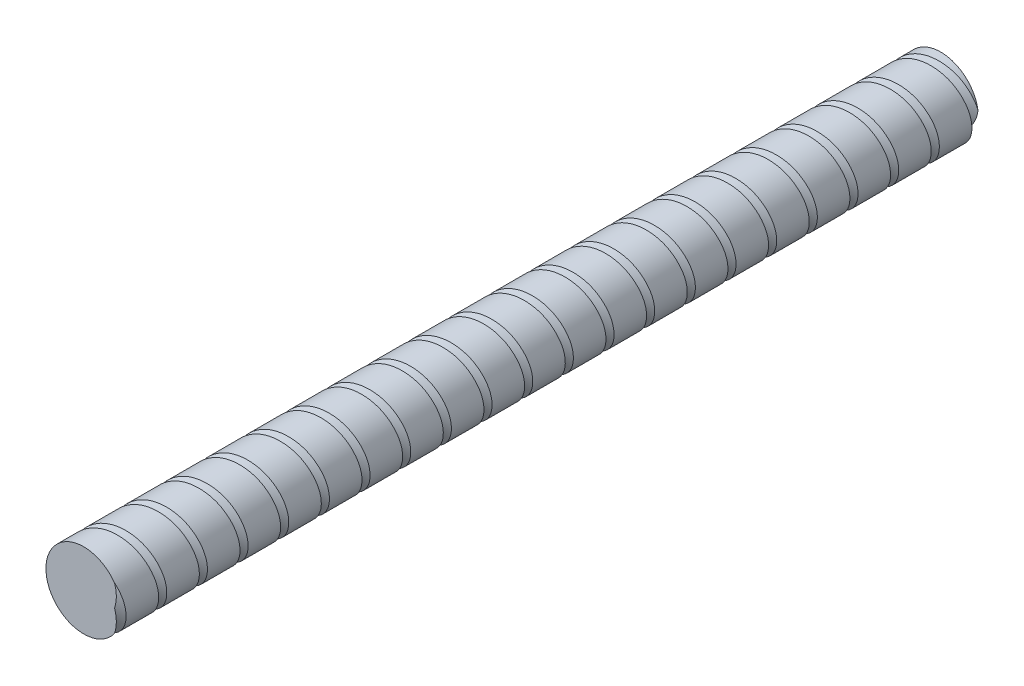
SolidWorks part; units mm, degrees
ref_plane "前视基准面" through (0, 0, 0) normal (0, 0, 1) x (1, 0, 0)
ref_plane "上视基准面" through (0, 0, 0) normal (0, 1, 0) x (1, 0, 0)
ref_plane "右视基准面" through (0, 0, 0) normal (1, 0, 0) x (0, 0, -1)
sketch "草图1" plane through (0, 0, 0) normal (0, 0, 1) x (1, 0, 0)
  circle A0 centre (0, 0) radius 6
  dimension "D1" = 12
extrude "凸台-拉伸1" add sketch "草图1" along normal mid plane 136.04
sketch "草图2" plane through (0, 0, 68.02) normal (0, 0, 1) x (1, 0, 0)
  circle A0 centre (0, 0) radius 6
curve "螺旋线/涡状线1" pitch 6.455 height 645.5 turns 100
sketch "草图3" plane through (0, 0, 0) normal (0, 1, 0) x (1, 0, 0)
  line L0 (6.0115, -67.37) -> (6.0115, -68.67)
  line L3 (6.0115, -68.67) -> (4.8857, -68.02)
  line L4 (-6, -68.02) -> (6, -68.02) construction
  line L5 (4.8857, -68.02) -> (6.0115, -67.37)
  dimension "D1" = 60
  dimension "D2" = 60
  dimension "D3" = 1.3
sweep "切除-扫描2" cut profiles "草图3" path "螺旋线/涡状线1"
